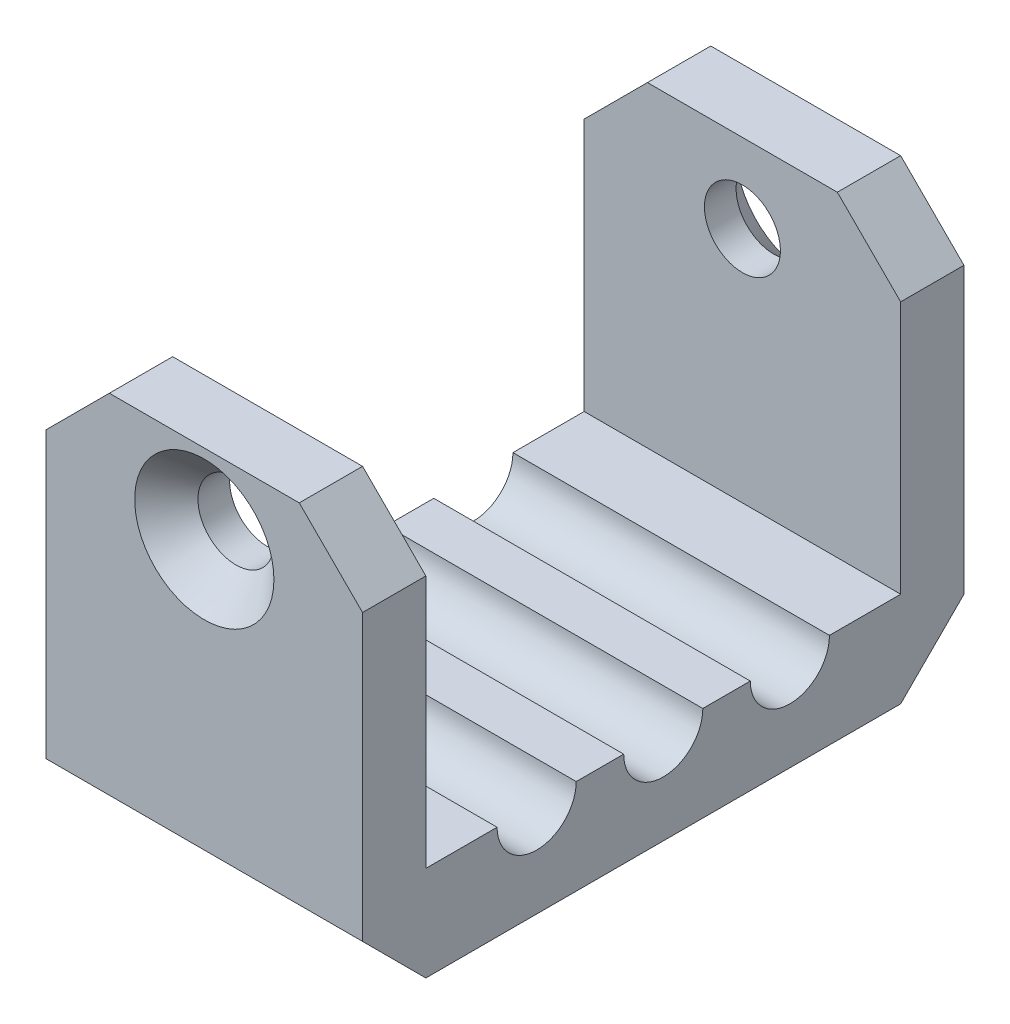
SolidWorks part; units mm, degrees
material "ABS PC"
ref_plane "Front Plane" through (0, 0, 0) normal (0, 0, 1) x (1, 0, 0)
ref_plane "Top Plane" through (0, 0, 0) normal (0, 1, 0) x (1, 0, 0)
ref_plane "Right Plane" through (0, 0, 0) normal (1, 0, 0) x (0, 0, -1)
sketch "Sketch1" plane through (0, 0, 0) normal (0, 1, 0) x (1, 0, 0)
  line L1 (-5, -7.5) -> (5, -7.5)
  line L2 (-5, -7.5) -> (-5, 7.5)
  line L3 (-5, 7.5) -> (5, 7.5)
  line L4 (5, -7.5) -> (5, 7.5)
  line L5 (-5, -7.5) -> (5, 7.5) construction
  line L6 (-5, 7.5) -> (5, -7.5) construction
  point P0 (0, 0)
  dimension "D1" = 10
  dimension "D2" = 15
extrude "Boss-Extrude1" add sketch "Sketch1" along normal blind 3
sketch "Sketch2" plane through (5, 0, 0) normal (1, 0, 0) x (0, 0, -1)
  line L0 (0, 5.6176) -> (0, -0.8561) construction
  line L1 (-4, 3) -> (0, 3) construction
  line L3 (-7.5, 3) -> (7.5, 3) construction
  circle A0 centre (0, 3) radius 1.25
  circle A1 centre (-4, 3) radius 1.25
  circle A2 centre (4, 3) radius 1.25
  dimension "D1" = 2.5
  dimension "D3" = 4
extrude "Cut-Extrude1" cut sketch "Sketch2" against normal through all
sketch "Sketch3" plane through (0, 0, 7.5) normal (0, 0, 1) x (1, 0, 0)
  line L0 (-5, 0) -> (5, 0) construction
  line L1 (5, 0) -> (-5, 0)
  line L2 (5, 0) -> (5, 13)
  line L3 (5, 13) -> (-5, 13)
  line L4 (-5, 0) -> (-5, 13)
  line L5 (-5, 3) -> (-5, 0) construction
  line L6 (-5, 3) -> (5, 3) construction
  point P6 (0, 0)
  point P7 (-5, 0)
  point P12 (4.0468, 10)
  point P13 (5, 0)
  dimension "D1" = 10
extrude "Boss-Extrude2" add sketch "Sketch3" along normal blind 2
mirror "Mirror1" about plane through (0, 0, 0) normal (0, 0, 1) of "Boss-Extrude2"
hole_wizard "CSK for M2 Flat Head Machine Screw1" positions "Sketch4" profile "Sketch5" countersink size "M2" standard "ANSI Metric"
sketch "Sketch4" plane through (0, 0, 9.5) normal (0, 0, 1) x (1, 0, 0)
  line L0 (0, 13) -> (0, 10.5) construction
  line L1 (5, 13) -> (-5, 13) construction
  point P0 (0, 10.5)
  dimension "D1" = 2.5
sketch "Sketch5" plane through (0, 10.5, 9.5) normal (1, 0, 0) x (0, -1, 0)
  line L0 (0, 0) -> (0, 5.721)
  line L1 (0, 5.721) -> (1.2, 5)
  line L2 (1.2, 5) -> (1.2, 1)
  line L3 (1.2, 1) -> (2.2, 0)
  line L5 (2.2, 0) -> (0, 0)
  line L6 (-1.2, 1) -> (-2.2, 0) construction
  line L10 (0, 5.721) -> (-1.2, 5) construction
  line L11 (0, -6.35) -> (0, 107.95) construction
  dimension "Hole Dia." = 2.4
  dimension "Hole Depth" = 5
  dimension "Near C'Sink Dia." = 4.4
  dimension "Near C'Sink Angle" = 90
  dimension "Drill Angle" = 118
mirror "Mirror2" about plane through (0, 0, 0) normal (0, 0, 1) of "CSK for M2 Flat Head Machine Screw1"
chamfer "Chamfer1" distance 2 angle 45 2 edges at (0, 0, -9.5) (0, 0, 9.5)
chamfer "Chamfer2" distance 2 angle 45 4 edges at (5, 13, -8.5) (-5, 13, -8.5) (5, 13, 8.5) (-5, 13, 8.5)
